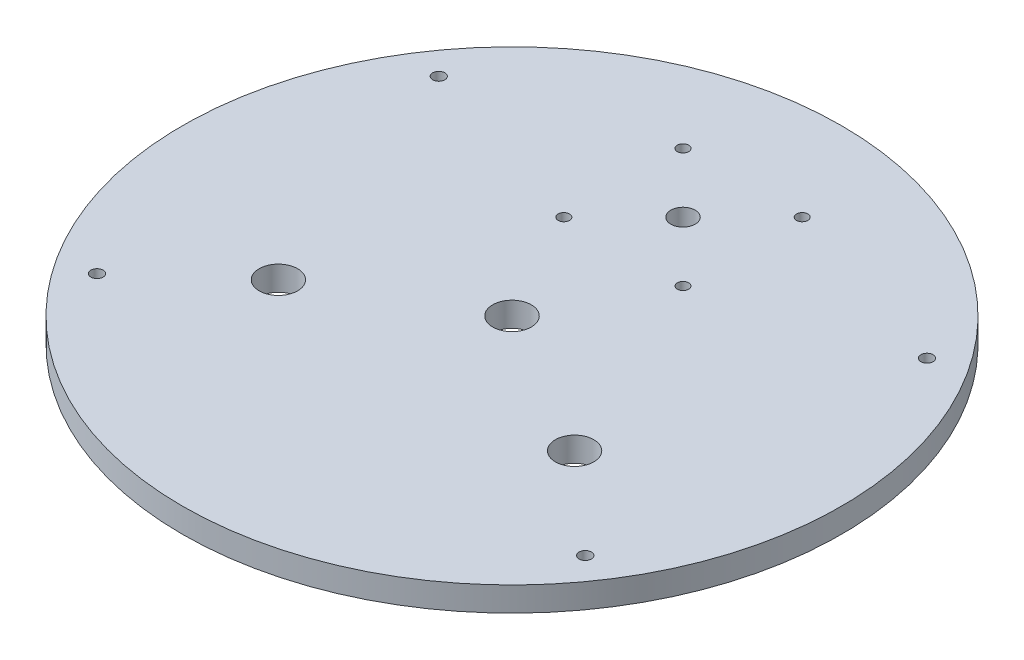
SolidWorks part; units mm, degrees
ref_plane "Front Plane" through (0, 0, 0) normal (0, 0, 1) x (1, 0, 0)
ref_plane "Top Plane" through (0, 0, 0) normal (0, 1, 0) x (1, 0, 0)
ref_plane "Right Plane" through (0, 0, 0) normal (1, 0, 0) x (0, 0, -1)
sketch "Sketch1" plane through (0, 0, 0) normal (0, 1, 0) x (1, 0, 0)
  circle A0 centre (0, 0) radius 85.725
  dimension "D1" = 171.45
extrude "Boss-Extrude1" add sketch "Sketch1" along normal blind 6.35
sketch "Sketch2" plane through (0, 6.35, 0) normal (0, 1, 0) x (1, 0, 0)
  line L0 (-63.5, 44.45) -> (-63.5, -44.45) construction
  line L1 (-63.5, -44.45) -> (63.5, -44.45) construction
  line L2 (63.5, -44.45) -> (63.5, 44.45) construction
  line L3 (63.5, 44.45) -> (-63.5, 44.45) construction
  circle A0 centre (-63.5, 44.45) radius 1.5875
  circle A1 centre (63.5, 44.45) radius 1.5875
  circle A2 centre (-63.5, -44.45) radius 1.5875
  circle A3 centre (63.5, -44.45) radius 1.5875
  dimension "D1" = 3.175
  dimension "D2" = 3.175
  dimension "D4" = 3.175
  dimension "D5" = 3.175
  dimension "D3" = 127
  dimension "D6" = 88.9
  dimension "D8" = 44.45
  dimension "D9" = 63.5
extrude "Cut-Extrude1" cut sketch "Sketch2" against normal up to next
sketch "Sketch3" plane through (0, 6.35, 0) normal (0, 1, 0) x (1, 0, 0)
  line L0 (0, 44.4823) -> (0, 0) construction
  line L1 (0, 0) -> (-38.5228, -22.2411) construction
  line L2 (0, 0) -> (38.5228, -22.2411) construction
  circle A0 centre (0, 44.4823) radius 3.175
  circle A1 centre (-38.5228, -22.2411) radius 5
  circle A2 centre (38.5228, -22.2411) radius 5
  dimension "D1" = 6.35
  dimension "D5" = 10
  dimension "D6" = 10
  dimension "D2" = 44.4823
  dimension "D3" = 120
  dimension "D4" = 120
extrude "Cut-Extrude2" cut sketch "Sketch3" against normal up to next contours A2 | A0 | A1 region at (38.5228, 6.35, 22.2411)
ref_axis "Axis1" through (0, 6.35, 0) along (0, -1, 0)
sketch "Sketch5" plane through (0, 6.35, 0) normal (0, 1, 0) x (1, 0, 0)
  line L1 (-15.5003, 59.9826) -> (15.5003, 59.9826) construction
  line L2 (-15.5003, 59.9826) -> (-15.5003, 28.9819) construction
  line L3 (-15.5003, 28.9819) -> (15.5004, 28.9819) construction
  line L4 (15.5003, 59.9826) -> (15.5004, 28.9819) construction
  line L5 (-15.5003, 59.9826) -> (15.5004, 28.9819) construction
  line L6 (-15.5003, 28.9819) -> (15.5003, 59.9826) construction
  circle A0 centre (0, 44.4823) radius 3.175 construction
  circle A1 centre (0, 44.4823) radius 3.175 construction
  circle A2 centre (-15.5003, 59.9826) radius 1.4732
  circle A3 centre (15.5003, 59.9826) radius 1.4732
  circle A4 centre (-15.5003, 28.9819) radius 1.4732
  circle A5 centre (15.5004, 28.9819) radius 1.4732
  dimension "D3" = 2.9464
  dimension "D4" = 2.9464
  dimension "D5" = 2.9464
  dimension "D6" = 2.9464
  dimension "D1" = 31.0007
  dimension "D2" = 31.0007
extrude "Cut-Extrude3" cut sketch "Sketch5" against normal up to next
sketch "Sketch6" plane through (0, 6.35, 0) normal (0, 1, 0) x (1, 0, 0)
  circle A0 centre (0, 0) radius 5.0165
  dimension "D1" = 10.033
extrude "center_hole" cut sketch "Sketch6" against normal up to next
equation "\"spur_gear_shaft_dist\"=1.75127"
equation "\"D2@Sketch3\"=\"spur_gear_shaft_dist\""
equation "\"D8@Sketch2\"=\"D6@Sketch2\"/2"
